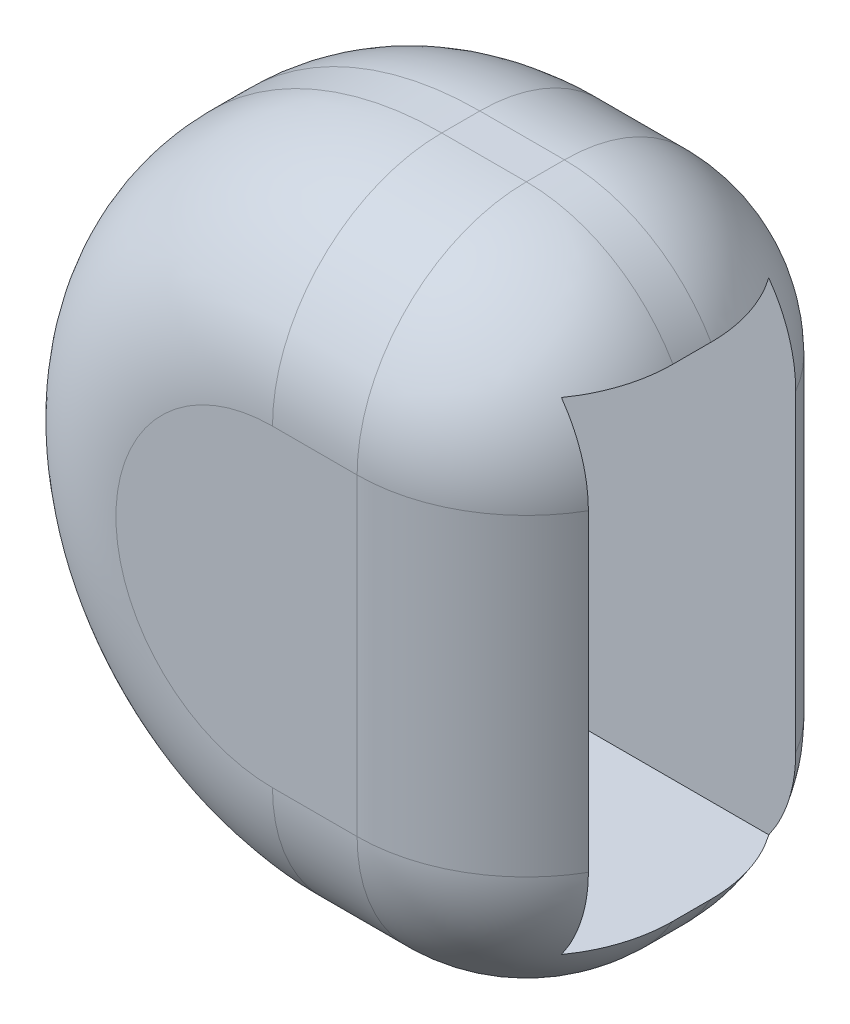
SolidWorks part; units mm, degrees
ref_plane "Front Plane" through (0, 0, 0) normal (0, 0, 1) x (1, 0, 0)
ref_plane "Top Plane" through (0, 0, 0) normal (0, 1, 0) x (1, 0, 0)
ref_plane "Right Plane" through (0, 0, 0) normal (1, 0, 0) x (0, 0, -1)
sketch "Sketch1" plane through (0, 0, 0) normal (0, 0, 1) x (1, 0, 0)
  line L0 (0, 14.25) -> (0, -14.25) construction
  line L4 (9.4875, 0) -> (-9.4875, 0) construction
  line L5 (0, 19.25) -> (15, 19.25)
  line L7 (15, -19.25) -> (0, -19.25)
  line L8 (10, 14.25) -> (10, -14.25) construction
  line L9 (0, 14.25) -> (10, 14.25) construction
  line L10 (10, -14.25) -> (0, -14.25) construction
  line L11 (0, -14.25) -> (15, -14.25)
  line L13 (15, 14.25) -> (0, 14.25)
  line L14 (15, 19.25) -> (15, -19.25) construction
  line L15 (15, 14.25) -> (15, 19.25)
  line L16 (15, -14.25) -> (15, -19.25)
  arc A0 (0, -14.25) -> (0, 14.25) centre (0, 0) cw
  arc A1 (0, -19.25) -> (0, 19.25) centre (0, 0) cw
  dimension "D3" = 14.25
  dimension "D1" = 5
  dimension "D2" = 5
  dimension "D5" = 15
  dimension "D6" = 15
  dimension "D4" = 5
extrude "Boss-Extrude1" add sketch "Sketch1" along normal blind 12.25
sketch "Sketch2" plane through (0, 0, 12.25) normal (0, 0, 1) x (1, 0, 0)
  line L0 (0, 19.25) -> (0, -19.25) construction
  line L1 (15, 19.25) -> (0, 19.25) construction
  line L2 (0, 19.25) -> (15, 19.25)
  line L4 (15, -19.25) -> (0, -19.25)
  line L5 (15, 19.25) -> (15, 14.25)
  line L6 (15, 14.25) -> (15, -14.25)
  line L7 (15, -14.25) -> (15, -19.25)
  arc A0 (0, 19.25) -> (0, -19.25) centre (0, 0) ccw
extrude "Boss-Extrude2" add sketch "Sketch2" along normal blind 5
pattern_linear "LPattern1" count 2 spacing 17.25 along (0, 0, -1) of "Boss-Extrude2"
fillet "Fillet11" radius 10 6 edges at (7.5, 19.25, 17.25) (7.5, -19.25, 17.25) (7.5, 19.25, -5) (7.5, -19.25, -5) (-19.25, 0, 17.25) (-19.25, 0, -5)
fillet "Fillet12" radius 10 8 edges at (15, -16.3211, 14.3211) (15, 0, 17.25) (15, 16.3211, 14.3211) (15, 19.25, 6.125) (15, 16.3211, -2.0711) (15, 0, -5) (15, -16.3211, -2.0711) (15, -19.25, 6.125)
